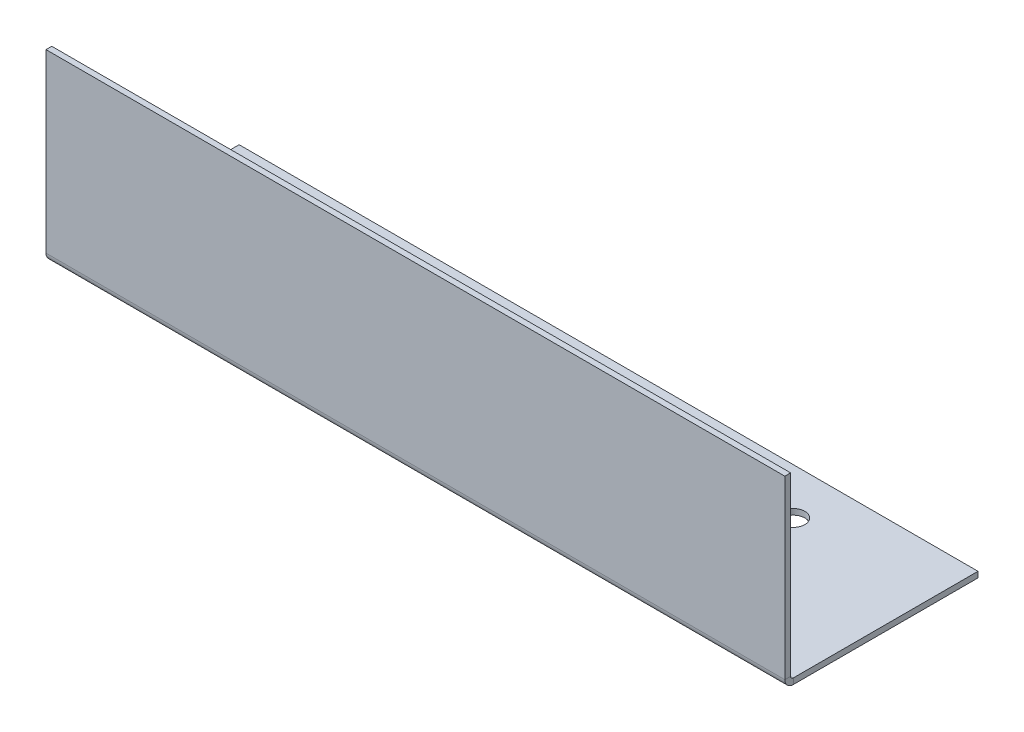
SolidWorks part; units mm, degrees
note: The reader was unsure of these and kept them because the rebuilt part matched: flange length of "Edge-Flange3".
ref_plane "Front Plane" through (0, 0, 0) normal (0, 0, 1) x (1, 0, 0)
ref_plane "Top Plane" through (0, 0, 0) normal (0, 1, 0) x (1, 0, 0)
ref_plane "Right Plane" through (0, 0, 0) normal (1, 0, 0) x (0, 0, -1)
sketch "Sketch1" plane through (0, 0, 0) normal (0, 1, 0) x (1, 0, 0)
  line L5 (-89.1273, 0) -> (-89.1273, 50.8)
  line L6 (-89.1273, 50.8) -> (114.0727, 50.8)
  line L11 (114.0727, 50.8) -> (114.0727, 0)
  line L16 (-89.1273, 0) -> (114.0727, 0)
  point P0 (0, 0)
  point P3 (12.4727, 0)
  point P4 (0, 0)
  dimension "D1" = 50.8
  dimension "D8" = 203.2
base flange "Base-Flange1" sketch "Sketch1" thickness 1.5875 reverse thickness direction no parameters "D1"=0.7366
edge flange "Edge-Flange3" sketch "Sketch14" flange angle 90 flange length 50.8 flange position bend outside bend radius 0.7366 thickness 1.5875 relief rectangular parameters "D6"=10
sketch "Sketch14" plane through (0, 0, 0) normal (0, 0, 1) x (1, 0, 0)
  line L0 (-89.1273, 0) -> (114.0727, 0) construction
  line L1 (-89.1273, 0) -> (114.0727, 0)
  line L2 (-89.1273, 0) -> (-89.1273, 49.2125)
  line L3 (-89.1273, 49.2125) -> (114.0727, 49.2125)
  line L4 (114.0727, 49.2125) -> (114.0727, 0)
bend "EdgeBend3" bend radius 0.7366 bend angle 90 parameters "D5"=1
sketch "Sketch15" plane through (0, 0, 0) normal (0, 1, 0) x (1, 0, 0)
  line L0 (75.9727, 50.8) -> (75.9727, 0) construction
  line L1 (114.0727, 50.8) -> (-89.1273, 50.8) construction
  line L2 (-89.1273, 0) -> (114.0727, 0) construction
  line L3 (114.0727, 0) -> (114.0727, 50.8) construction
  line L4 (-51.0273, 50.8) -> (-51.0273, 0) construction
  line L5 (-89.1273, 50.8) -> (-89.1273, 0) construction
  circle A0 centre (-51.0273, 38.1) radius 3.175
  circle A1 centre (75.9727, 38.1) radius 3.175
  circle A2 centre (-51.0273, 12.7) radius 3.175
  circle A3 centre (75.9727, 12.7) radius 3.175
  point P14 (0, 0)
  point P15 (0, 0)
  dimension "D1" = 6.35
  dimension "D2" = 6.35
  dimension "D3" = 6.35
  dimension "D4" = 6.35
  dimension "D5" = 38.1
  dimension "D6" = 38.1
  dimension "D7" = 12.7
  dimension "D8" = 12.7
  dimension "D9" = 12.7
  dimension "D10" = 12.7
extrude "Cut-Extrude1" cut sketch "Sketch15" against normal up to surface (1.5875 mm away) normal cut yes up to face at (12.4727, -1.5875, -25.4)
sketch "Bend-Lines1" [suppressed] plane through (0, 0, 0) normal (0, 1, 0) x (1, 0, 0)
sketch "Bounding-Box1" [suppressed] plane through (0, 0, 0) normal (0, 1, 0) x (1, 0, 0)
sheet metal parameters "Sheet-Metal1" thickness 1.5875 parameters "D1"=0.7366
flat pattern "Flat-Pattern1" [suppressed]
sketch "Bend-Lines2" plane through (0, 0, 0) normal (0, 1, 0) x (1, 0, 0)
sketch3d "Bounding-Box2" [suppressed]
  line L0 (-89.1273, 0, 0) -> (-89.1273, 101.6, 0) construction
  line L1 (-12.9273, 0, 0) -> (-12.9273, 101.6, 0) construction
  line L2 (-89.1273, 0, 0) -> (-12.9273, 0, 0) construction
  line L3 (-89.1273, 101.6, 0) -> (-12.9273, 101.6, 0) construction
sheet metal parameters "Sheet-Metal4" thickness 1.5875 parameters "D1"=0.7366
flat pattern "Flat-Pattern1"
sketch "Bend-Lines2" plane through (0, 0, 0) normal (0, 1, 0) x (1, 0, 0)
  line L0 (-89.1273, -1.2019) -> (114.0727, -1.2019) construction
  line L1 (-89.1273, -1.2019) -> (114.0727, -1.2019) construction
sketch3d "Bounding-Box2" [suppressed]
  line L0 (114.0727, 50.8, 0) -> (-89.1273, 50.8, 0) construction
  line L1 (114.0727, -50.8798, 0) -> (-89.1273, -50.8798, 0) construction
  line L2 (114.0727, 50.8, 0) -> (114.0727, -50.8798, 0) construction
  line L3 (-89.1273, 50.8, 0) -> (-89.1273, -50.8798, 0) construction
bend of the flat pattern "Flatten-<EdgeBend3>1"
sheet metal parameters "Sheet-Metal5" thickness 1.5875 parameters "D1"=0.7366
flat pattern "Flat-Pattern1"
sketch "Bend-Lines2" plane through (0, 0, 0) normal (0, 1, 0) x (1, 0, 0)
  line L0 (-89.1273, -1.2019) -> (114.0727, -1.2019) construction
  line L1 (-89.1273, -1.2019) -> (114.0727, -1.2019) construction
sketch3d "Bounding-Box2" [suppressed]
  line L0 (114.0727, 50.8, 0) -> (-89.1273, 50.8, 0) construction
  line L1 (114.0727, -50.8798, 0) -> (-89.1273, -50.8798, 0) construction
  line L2 (114.0727, 50.8, 0) -> (114.0727, -50.8798, 0) construction
  line L3 (-89.1273, 50.8, 0) -> (-89.1273, -50.8798, 0) construction
bend of the flat pattern "Flatten-<EdgeBend3>1"
